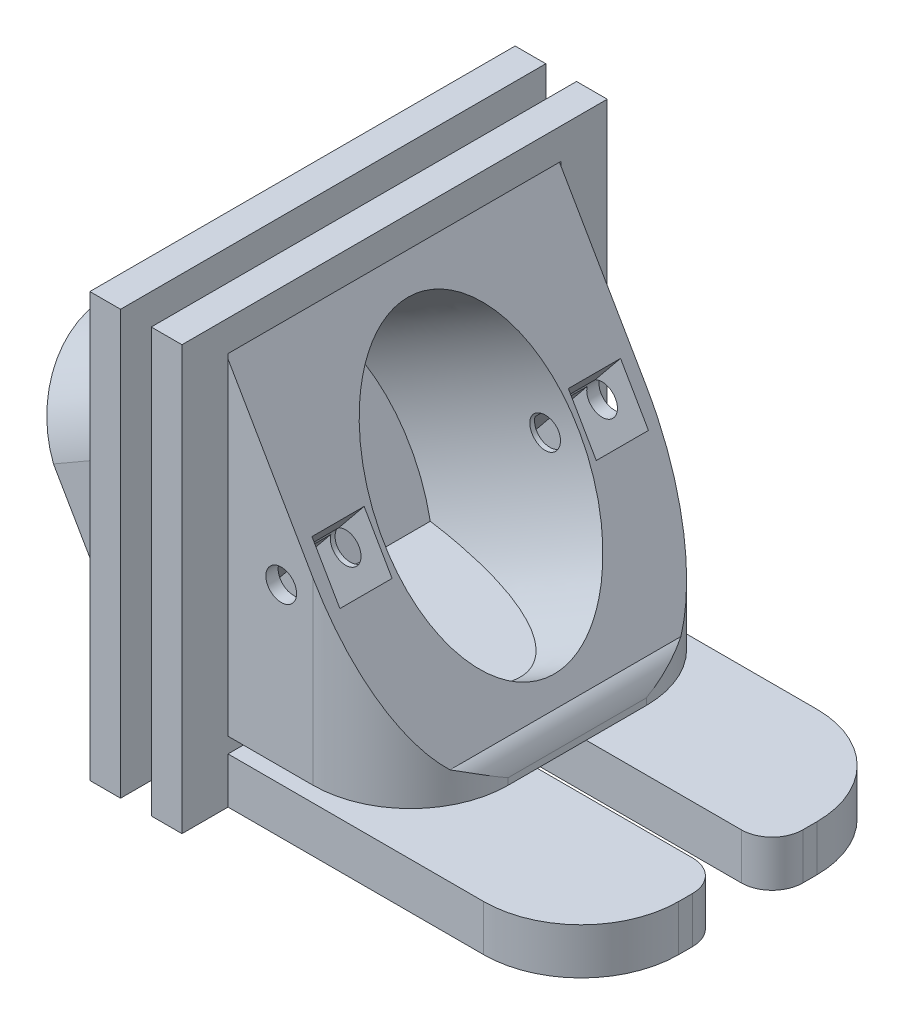
SolidWorks part; units mm, degrees
note: The reader was unsure of these and kept them because the rebuilt part matched: shared geometry of "Sketch7<3>".
ref_plane "Front Plane" through (0, 0, 0) normal (0, 0, 1) x (1, 0, 0)
ref_plane "Top Plane" through (0, 0, 0) normal (0, 1, 0) x (1, 0, 0)
ref_plane "Right Plane" through (0, 0, 0) normal (1, 0, 0) x (0, 0, -1)
sketch "Sketch1" plane through (0, 0, 0) normal (0, 0, 1) x (1, 0, 0)
  line L0 (0, 0) -> (16.4978, 9.525)
  line L1 (0, 0) -> (20.7767, 0) construction
  line L2 (12.7, 0) -> (19.6728, 4.0257)
  line L3 (19.6928, 3.9911) -> (16.4978, 9.525) construction
  point P9 (14.1735, 0.8507)
  dimension "D1" = 19.05
  dimension "D2" = 30
  dimension "D3" = 6.35
  dimension "D4" = 8.0515
  dimension "D5" = 6.35
ref_plane "Plane1" through (16.4978, 9.525, 0) normal (0.866, 0.5, 0) x (0, 0, -1)
sketch "Sketch2" plane through (16.4978, 9.525, 0) normal (0.866, 0.5, 0) x (0, 0, -1)
  line L0 (0, 100000) -> (0, -100010.3884) construction
  line L1 (10.85, 12.525) -> (10.85, -12.525)
  line L2 (10.85, 12.525) -> (-10.85, 12.525)
  line L3 (10.85, -12.525) -> (-10.85, -12.525)
  line L4 (-10.85, 12.525) -> (-10.85, -12.525)
  line L5 (10.85, 12.525) -> (-10.85, -12.525) construction
  line L6 (10.85, -12.525) -> (-10.85, 12.525) construction
  ellipse E0 centre (0, 0) end of major axis (0, 9.525) minor radius 6.35
  point P1 (-10.85, 0)
  point P7 (0, -12.525)
  dimension "D1" = 19.05
  dimension "D2" = 12.7
  dimension "D3" = 4.5
  dimension "D4" = 3
extrude "Boss-Extrude1" add sketch "Sketch2" against normal blind 12.7
sketch "Sketch3" plane through (5.4993, 3.175, 0) normal (-0.866, -0.5, 0) x (0, 0, 1)
  line L0 (-10.85, 12.525) -> (-10.85, -12.525)
  line L1 (-10.85, 12.525) -> (10.8107, 12.525)
  line L2 (-10.85, -12.525) -> (10.8107, -12.525)
  line L3 (10.8107, 12.525) -> (10.8107, -12.525)
extrude "Boss-Extrude2" add sketch "Sketch3" along normal blind 3
sketch "Sketch5" plane through (0, 0, 0) normal (0, 1, 0) x (-1, 0, 0)
  line L0 (-22.7603, 10.85) -> (-22.7603, -10.85)
  line L1 (-22.7603, 10.85) -> (-3.8682, 10.85)
  line L2 (-22.7603, -10.85) -> (-3.8682, -10.85)
  line L3 (-3.8682, 10.85) -> (-3.8682, -10.85)
  line L8 (-22.7603, 10.85) -> (-22.7603, -10.85) construction
extrude "Boss-Extrude3" add sketch "Sketch5" against normal blind 2
sketch "Sketch6" plane through (0, -2, 0) normal (0, -1, 0) x (1, 0, 0)
  line L0 (3.8682, -10.85) -> (3.8682, 10.85)
  line L1 (3.8682, -10.85) -> (33.8682, -10.85)
  line L2 (3.8682, 10.85) -> (33.8682, 10.85)
  line L3 (33.8682, -10.85) -> (33.8682, 10.85)
  line L10 (3.8682, 10.85) -> (8.487, 10.85) construction
  line L11 (3.8682, -10.85) -> (3.8682, 10.85) construction
  dimension "D1" = 30
extrude "Boss-Extrude4" add sketch "Sketch6" along normal blind 4
sketch "Sketch7" plane through (33.8682, 0, 0) normal (1, 0, 0) x (0, 0, -1)
  line L0 (-10.85, -2) -> (10.85, -2)
  line L1 (-10.85, -2) -> (-10.85, -3)
  line L2 (10.85, -2) -> (10.85, -3)
  line L3 (-10.85, -3) -> (10.85, -3)
  line L4 (-1.5875, -3) -> (1.5875, -3)
  line L5 (-10.85, -6) -> (-10.85, -2) construction
  line L6 (-10.85, -6) -> (10.85, -6)
  line L7 (-10.85, -6) -> (-10.85, -13.2725)
  line L8 (10.85, -6) -> (10.85, -13.2725)
  line L9 (-10.85, -13.2725) -> (10.85, -13.2725)
  line L10 (-1.5875, -3) -> (-1.5875, -6)
  line L11 (1.5875, -3) -> (1.5875, -6)
  line L12 (-1.5875, -6) -> (1.5875, -6)
  point P0 (0, -3)
  point P11 (0, -3)
  line M4 (-10.85, -6) -> (10.85, -6)
  dimension "D1" = 1
  dimension "D2" = 3.175
extrude "Cut-Extrude2" cut sketch "Sketch7" against normal blind 23 contours L2 L3 L1 L0 | L10 L12 L11 L4
extrude "Cut-Extrude3" cut sketch "Sketch7<3>" against normal through all contours L7 L9 L8 M4
sketch "Sketch7<3>" plane through (33.8682, 0, 0) normal (1, 0, 0) x (0, 0, -1) same geometry as "Sketch7"
ref_plane "Plane2" through (3.175, -5.4993, 0) normal (0.5, -0.866, 0) x (0.866, 0.5, 0)
sketch "Sketch8" plane through (3.175, -5.4993, 6.35) normal (0.5, -0.866, 0) x (0.75, 0.433, -0.5)
  line L0 (13.7985, 1.5003) -> (14.5485, 0.2012)
  line L1 (13.7985, 1.5003) -> (-3.522, -8.4997)
  line L2 (14.5485, 0.2012) -> (-2.772, -9.7988)
  line L3 (-3.522, -8.4997) -> (-2.772, -9.7988)
  line L4 (12.7, 0) -> (19.6728, 4.0257) construction
  dimension "D1" = 1.5
  dimension "D2" = 20
ref_plane "Plane3" through (19.6728, 0, 0) normal (1, 0, 0) x (0, 0, -1)
sketch "Sketch11" plane through (19.6728, 0.1949, 0) normal (-1, 0, 0) x (0, 0, -1)
  circle A0 centre (0, -3.8309) radius 1
  dimension "D1" = 2
extrude "Cut-Extrude8" cut sketch "Sketch11" along normal through all
sketch "Sketch13" plane through (0, 0, 0) normal (0, 0, 1) x (1, 0, 0)
  line L0 (16.4978, 9.525) -> (3.8682, -6)
sketch "Sketch9" plane through (0, 0, -10.85) normal (0, 0, -1) x (-1, 0, 0)
  line L0 (0, 0) -> (-16.4978, 9.525) construction
  line L1 (-10.2353, 20.372) -> (-21.997, 0) construction
  circle A0 centre (-14.3327, 8.275) radius 1
  dimension "D1" = 2
  dimension "D2" = 2.5
extrude "Cut-Extrude4" cut sketch "Sketch9" against normal up to next contours A0
ref_plane "Plane4" through (16.4978, 9.525, 0) normal (0.6311, 0.7757, 0) x (0.7757, -0.6311, 0)
sketch "Sketch15" plane through (16.4978, 9.525, 0) normal (0.6311, 0.7757, 0) x (0.7757, -0.6311, 0)
  line L0 (-11.7031, -10.85) -> (10.2768, -10.85) construction
  line L1 (-1.8, -6.65) -> (1.6, -6.65)
  line L2 (-1.8, -6.65) -> (-1.8, -10.05)
  line L3 (-1.8, -10.05) -> (1.6, -10.05)
  line L4 (1.6, -6.65) -> (1.6, -10.05)
  line L5 (-0.8907, -8.6694) -> (-0.8907, 3.3485) construction
  line L6 (0, 0) -> (0, -5.6108) construction
  dimension "D1" = 3.4
  dimension "D2" = 1.6
  dimension "D3" = 0.8
  dimension "D4" = 1.8
  dimension "D5" = 2.4907
extrude "Cut-Extrude9" cut sketch "Sketch15" against normal through all both and the other way through all
ref_plane "Plane5" through (8.8682, 0, 0) normal (1, 0, 0) x (0, 0, -1)
sketch "Sketch16" plane through (8.8682, 0, 0) normal (1, 0, 0) x (0, 0, -1)
  line L0 (-10.85, -6) -> (-10.85, 19.5827)
  line L1 (-10.85, -6) -> (-13.85, -6)
  line L2 (-13.85, -6) -> (-13.85, 21.5827)
  line L3 (-13.85, 21.5827) -> (0, 21.5827)
  line L4 (0, 0.4107) -> (0, 31.1328) construction
  line L5 (0, 19.5827) -> (0, 21.5827)
  line L9 (-10.85, 19.5827) -> (0, 19.5827)
  dimension "D1" = 2
  dimension "D2" = 3
extrude "Boss-Extrude5" add sketch "Sketch16" along normal blind 2
ref_plane "Plane17" through (6.8682, 0, 0) normal (-1, 0, 0) x (0, 0, 1)
sketch "Sketch18" plane through (6.8682, 0, 0) normal (-1, 0, 0) x (0, 0, 1)
  line L0 (10.85, -6) -> (13.85, -6)
  line L1 (13.85, -6) -> (13.85, 21.5827)
  line L2 (13.85, 21.5827) -> (0, 21.5827)
  line L3 (0, 21.5827) -> (0, 14.5827)
  line L4 (0, -173201.0896) -> (0, 173214.6058) construction
  line L5 (0, 14.5827) -> (10.85, 14.5827)
  line L6 (10.85, 14.022) -> (10.85, 19.5827) construction
  line L7 (10.85, 14.5827) -> (10.85, -6)
  dimension "D1" = 7
extrude "Boss-Extrude6" add sketch "Sketch18" along normal blind 2
mirror "Mirror1" about plane through (0, 0, 0) normal (0, 0, 1) of "Boss-Extrude6", "Boss-Extrude5", "Cut-Extrude9", "Cut-Extrude4"
fillet "Fillet5" radius 6.35 10 edges at (-0.7632, 14.022, 10.8303) (-2.0623, 13.272, 10.8107) (22.7603, -1, 10.85) (22.7603, -1, -10.85) (22.3787, 0, 10.85) (22.3787, 0, -10.85) (0.7535, 14.8976, -10.85) (2.0525, 15.6476, 10.85) (33.8682, -4.5, -10.85) (33.8682, -4.5, 10.85)
fillet "Fillet6" radius 2 2 edges at (33.8682, -4.5, -1.5875) (33.8682, -4.5, 1.5875)
fillet "Fillet7" radius 2 1 edges at (22.7603, 0, 0)
sketch "Sketch19" plane through (0, 0, 10.85) normal (0, 0, 1) x (1, 0, 0)
  line L1 (8.8682, 21.5827) -> (8.8682, 17.5827)
  line L2 (8.8682, 17.5827) -> (6.8682, 17.5827)
  line L3 (6.8682, 17.5827) -> (6.8682, 21.5827)
  line L4 (8.8682, 21.5827) -> (8.8682, -6) construction
  line L5 (6.8682, -6) -> (6.8682, 18.428) construction
  line L6 (10.8682, 21.5827) -> (8.8682, 21.5827) construction
  line L8 (8.8682, 21.5827) -> (6.8682, 21.5827)
  dimension "D1" = 4
extrude "Cut-Extrude10" cut sketch "Sketch19" against normal through all
